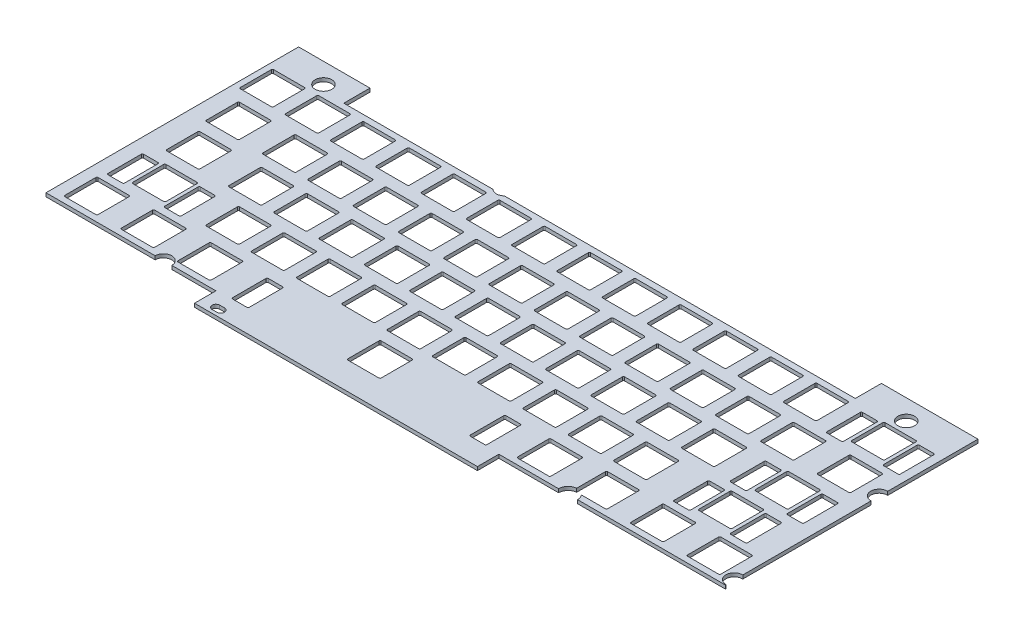
SolidWorks part; units mm, degrees
ref_plane "前视基准面" through (0, 0, 0) normal (0, 0, 1) x (1, 0, 0)
ref_plane "上视基准面" through (0, 0, 0) normal (0, 1, 0) x (1, 0, 0)
ref_plane "右视基准面" through (0, 0, 0) normal (1, 0, 0) x (0, 0, -1)
other "Configuration Table"
sketch "草图3" plane through (0, 0, 0) normal (0, 1, 0) x (1, 0, 0)
  line L0 (3.025, -2.525) -> (16.025, -2.525)
  line L1 (3.025, -16.525) -> (16.025, -16.525)
  line L2 (2.525, -3.025) -> (2.525, -16.025)
  line L3 (16.525, -3.025) -> (16.525, -16.025)
  line L4 (22.075, -2.525) -> (35.075, -2.525)
  line L5 (22.075, -16.525) -> (35.075, -16.525)
  line L6 (21.575, -3.025) -> (21.575, -16.025)
  line L7 (35.575, -3.025) -> (35.575, -16.025)
  line L8 (41.125, -2.525) -> (54.125, -2.525)
  line L9 (41.125, -16.525) -> (54.125, -16.525)
  line L10 (40.625, -3.025) -> (40.625, -16.025)
  line L11 (54.625, -3.025) -> (54.625, -16.025)
  line L12 (60.175, -2.525) -> (73.175, -2.525)
  line L13 (60.175, -16.525) -> (73.175, -16.525)
  line L14 (59.675, -3.025) -> (59.675, -16.025)
  line L15 (73.675, -3.025) -> (73.675, -16.025)
  line L16 (79.225, -2.525) -> (92.225, -2.525)
  line L17 (79.225, -16.525) -> (92.225, -16.525)
  line L18 (78.725, -3.025) -> (78.725, -16.025)
  line L19 (92.725, -3.025) -> (92.725, -16.025)
  line L20 (98.275, -2.525) -> (111.275, -2.525)
  line L21 (98.275, -16.525) -> (111.275, -16.525)
  line L22 (97.775, -3.025) -> (97.775, -16.025)
  line L23 (111.775, -3.025) -> (111.775, -16.025)
  line L24 (117.325, -2.525) -> (130.325, -2.525)
  line L25 (117.325, -16.525) -> (130.325, -16.525)
  line L26 (116.825, -3.025) -> (116.825, -16.025)
  line L27 (130.825, -3.025) -> (130.825, -16.025)
  line L28 (136.375, -2.525) -> (149.375, -2.525)
  line L29 (136.375, -16.525) -> (149.375, -16.525)
  line L30 (135.875, -3.025) -> (135.875, -16.025)
  line L31 (149.875, -3.025) -> (149.875, -16.025)
  line L32 (155.425, -2.525) -> (168.425, -2.525)
  line L33 (155.425, -16.525) -> (168.425, -16.525)
  line L34 (154.925, -3.025) -> (154.925, -16.025)
  line L35 (168.925, -3.025) -> (168.925, -16.025)
  line L36 (174.475, -2.525) -> (187.475, -2.525)
  line L37 (174.475, -16.525) -> (187.475, -16.525)
  line L38 (173.975, -3.025) -> (173.975, -16.025)
  line L39 (187.975, -3.025) -> (187.975, -16.025)
  line L40 (193.525, -2.525) -> (206.525, -2.525)
  line L41 (193.525, -16.525) -> (206.525, -16.525)
  line L42 (193.025, -3.025) -> (193.025, -16.025)
  line L43 (207.025, -3.025) -> (207.025, -16.025)
  line L44 (212.575, -2.525) -> (225.575, -2.525)
  line L45 (212.575, -16.525) -> (225.575, -16.525)
  line L46 (212.075, -3.025) -> (212.075, -16.025)
  line L47 (226.075, -3.025) -> (226.075, -16.025)
  line L48 (231.625, -2.525) -> (244.625, -2.525)
  line L49 (231.625, -16.525) -> (244.625, -16.525)
  line L50 (231.125, -3.025) -> (231.125, -16.025)
  line L51 (245.125, -3.025) -> (245.125, -16.025)
  line L52 (260.2, -2.525) -> (273.2, -2.525)
  line L53 (260.2, -16.525) -> (273.2, -16.525)
  line L54 (259.7, -3.025) -> (259.7, -16.025)
  line L55 (273.7, -3.025) -> (273.7, -16.025)
  line L56 (251.762, -3.525) -> (257.762, -3.525)
  line L57 (251.762, -18.525) -> (257.762, -18.525)
  line L58 (251.262, -4.025) -> (251.262, -18.025)
  line L59 (258.262, -4.025) -> (258.262, -18.025)
  line L60 (275.638, -3.525) -> (281.638, -3.525)
  line L61 (275.638, -18.525) -> (281.638, -18.525)
  line L62 (275.138, -4.025) -> (275.138, -18.025)
  line L63 (282.138, -4.025) -> (282.138, -18.025)
  line L64 (7.7875, -21.575) -> (20.7875, -21.575)
  line L65 (7.7875, -35.575) -> (20.7875, -35.575)
  line L66 (7.2875, -22.075) -> (7.2875, -35.075)
  line L67 (21.2875, -22.075) -> (21.2875, -35.075)
  line L68 (31.6, -21.575) -> (44.6, -21.575)
  line L69 (31.6, -35.575) -> (44.6, -35.575)
  line L70 (31.1, -22.075) -> (31.1, -35.075)
  line L71 (45.1, -22.075) -> (45.1, -35.075)
  line L72 (50.65, -21.575) -> (63.65, -21.575)
  line L73 (50.65, -35.575) -> (63.65, -35.575)
  line L74 (50.15, -22.075) -> (50.15, -35.075)
  line L75 (64.15, -22.075) -> (64.15, -35.075)
  line L76 (69.7, -21.575) -> (82.7, -21.575)
  line L77 (69.7, -35.575) -> (82.7, -35.575)
  line L78 (69.2, -22.075) -> (69.2, -35.075)
  line L79 (83.2, -22.075) -> (83.2, -35.075)
  line L80 (88.75, -21.575) -> (101.75, -21.575)
  line L81 (88.75, -35.575) -> (101.75, -35.575)
  line L82 (88.25, -22.075) -> (88.25, -35.075)
  line L83 (102.25, -22.075) -> (102.25, -35.075)
  line L84 (107.8, -21.575) -> (120.8, -21.575)
  line L85 (107.8, -35.575) -> (120.8, -35.575)
  line L86 (107.3, -22.075) -> (107.3, -35.075)
  line L87 (121.3, -22.075) -> (121.3, -35.075)
  line L88 (126.85, -21.575) -> (139.85, -21.575)
  line L89 (126.85, -35.575) -> (139.85, -35.575)
  line L90 (126.35, -22.075) -> (126.35, -35.075)
  line L91 (140.35, -22.075) -> (140.35, -35.075)
  line L92 (145.9, -21.575) -> (158.9, -21.575)
  line L93 (145.9, -35.575) -> (158.9, -35.575)
  line L94 (145.4, -22.075) -> (145.4, -35.075)
  line L95 (159.4, -22.075) -> (159.4, -35.075)
  line L96 (164.95, -21.575) -> (177.95, -21.575)
  line L97 (164.95, -35.575) -> (177.95, -35.575)
  line L98 (164.45, -22.075) -> (164.45, -35.075)
  line L99 (178.45, -22.075) -> (178.45, -35.075)
  line L100 (184, -21.575) -> (197, -21.575)
  line L101 (184, -35.575) -> (197, -35.575)
  line L102 (183.5, -22.075) -> (183.5, -35.075)
  line L103 (197.5, -22.075) -> (197.5, -35.075)
  line L104 (203.05, -21.575) -> (216.05, -21.575)
  line L105 (203.05, -35.575) -> (216.05, -35.575)
  line L106 (202.55, -22.075) -> (202.55, -35.075)
  line L107 (216.55, -22.075) -> (216.55, -35.075)
  line L108 (222.1, -21.575) -> (235.1, -21.575)
  line L109 (222.1, -35.575) -> (235.1, -35.575)
  line L110 (221.6, -22.075) -> (221.6, -35.075)
  line L111 (235.6, -22.075) -> (235.6, -35.075)
  line L112 (241.15, -21.575) -> (254.15, -21.575)
  line L113 (241.15, -35.575) -> (254.15, -35.575)
  line L114 (240.65, -22.075) -> (240.65, -35.075)
  line L115 (254.65, -22.075) -> (254.65, -35.075)
  line L116 (264.9625, -21.575) -> (277.9625, -21.575)
  line L117 (264.9625, -35.575) -> (277.9625, -35.575)
  line L118 (264.4625, -22.075) -> (264.4625, -35.075)
  line L119 (278.4625, -22.075) -> (278.4625, -35.075)
  line L120 (10.1687, -40.625) -> (23.1687, -40.625)
  line L121 (10.1687, -54.625) -> (23.1687, -54.625)
  line L122 (9.6688, -41.125) -> (9.6688, -54.125)
  line L123 (23.6687, -41.125) -> (23.6687, -54.125)
  line L124 (36.3625, -40.625) -> (49.3625, -40.625)
  line L125 (36.3625, -54.625) -> (49.3625, -54.625)
  line L126 (35.8625, -41.125) -> (35.8625, -54.125)
  line L127 (49.8625, -41.125) -> (49.8625, -54.125)
  line L128 (55.4125, -40.625) -> (68.4125, -40.625)
  line L129 (55.4125, -54.625) -> (68.4125, -54.625)
  line L130 (54.9125, -41.125) -> (54.9125, -54.125)
  line L131 (68.9125, -41.125) -> (68.9125, -54.125)
  line L132 (74.4625, -40.625) -> (87.4625, -40.625)
  line L133 (74.4625, -54.625) -> (87.4625, -54.625)
  line L134 (73.9625, -41.125) -> (73.9625, -54.125)
  line L135 (87.9625, -41.125) -> (87.9625, -54.125)
  line L136 (93.5125, -40.625) -> (106.5125, -40.625)
  line L137 (93.5125, -54.625) -> (106.5125, -54.625)
  line L138 (93.0125, -41.125) -> (93.0125, -54.125)
  line L139 (107.0125, -41.125) -> (107.0125, -54.125)
  line L140 (112.5625, -40.625) -> (125.5625, -40.625)
  line L141 (112.5625, -54.625) -> (125.5625, -54.625)
  line L142 (112.0625, -41.125) -> (112.0625, -54.125)
  line L143 (126.0625, -41.125) -> (126.0625, -54.125)
  line L144 (131.6125, -40.625) -> (144.6125, -40.625)
  line L145 (131.6125, -54.625) -> (144.6125, -54.625)
  line L146 (131.1125, -41.125) -> (131.1125, -54.125)
  line L147 (145.1125, -41.125) -> (145.1125, -54.125)
  line L148 (150.6625, -40.625) -> (163.6625, -40.625)
  line L149 (150.6625, -54.625) -> (163.6625, -54.625)
  line L150 (150.1625, -41.125) -> (150.1625, -54.125)
  line L151 (164.1625, -41.125) -> (164.1625, -54.125)
  line L152 (169.7125, -40.625) -> (182.7125, -40.625)
  line L153 (169.7125, -54.625) -> (182.7125, -54.625)
  line L154 (169.2125, -41.125) -> (169.2125, -54.125)
  line L155 (183.2125, -41.125) -> (183.2125, -54.125)
  line L156 (188.7625, -40.625) -> (201.7625, -40.625)
  line L157 (188.7625, -54.625) -> (201.7625, -54.625)
  line L158 (188.2625, -41.125) -> (188.2625, -54.125)
  line L159 (202.2625, -41.125) -> (202.2625, -54.125)
  line L160 (207.8125, -40.625) -> (220.8125, -40.625)
  line L161 (207.8125, -54.625) -> (220.8125, -54.625)
  line L162 (207.3125, -41.125) -> (207.3125, -54.125)
  line L163 (221.3125, -41.125) -> (221.3125, -54.125)
  line L164 (226.8625, -40.625) -> (239.8625, -40.625)
  line L165 (226.8625, -54.625) -> (239.8625, -54.625)
  line L166 (226.3625, -41.125) -> (226.3625, -54.125)
  line L167 (240.3625, -41.125) -> (240.3625, -54.125)
  line L168 (257.8188, -40.625) -> (270.8188, -40.625)
  line L169 (257.8188, -54.625) -> (270.8188, -54.625)
  line L170 (257.3188, -41.125) -> (257.3188, -54.125)
  line L171 (271.3188, -41.125) -> (271.3188, -54.125)
  line L172 (249.3808, -41.625) -> (255.3807, -41.625)
  line L173 (249.3808, -56.625) -> (255.3807, -56.625)
  line L174 (248.8808, -42.125) -> (248.8808, -56.125)
  line L175 (255.8807, -42.125) -> (255.8807, -56.125)
  line L176 (273.2568, -41.625) -> (279.2568, -41.625)
  line L177 (273.2568, -56.625) -> (279.2568, -56.625)
  line L178 (272.7568, -42.125) -> (272.7568, -56.125)
  line L179 (279.7568, -42.125) -> (279.7568, -56.125)
  line L180 (14.9313, -59.675) -> (27.9312, -59.675)
  line L181 (14.9313, -73.675) -> (27.9312, -73.675)
  line L182 (14.4313, -60.175) -> (14.4313, -73.175)
  line L183 (28.4312, -60.175) -> (28.4312, -73.175)
  line L184 (6.4932, -60.675) -> (12.4932, -60.675)
  line L185 (6.4932, -75.675) -> (12.4932, -75.675)
  line L186 (5.9932, -61.175) -> (5.9932, -75.175)
  line L187 (12.9932, -61.175) -> (12.9932, -75.175)
  line L188 (30.3693, -60.675) -> (36.3693, -60.675)
  line L189 (30.3693, -75.675) -> (36.3693, -75.675)
  line L190 (29.8693, -61.175) -> (29.8693, -75.175)
  line L191 (36.8693, -61.175) -> (36.8693, -75.175)
  line L192 (45.8875, -59.675) -> (58.8875, -59.675)
  line L193 (45.8875, -73.675) -> (58.8875, -73.675)
  line L194 (45.3875, -60.175) -> (45.3875, -73.175)
  line L195 (59.3875, -60.175) -> (59.3875, -73.175)
  line L196 (64.9375, -59.675) -> (77.9375, -59.675)
  line L197 (64.9375, -73.675) -> (77.9375, -73.675)
  line L198 (64.4375, -60.175) -> (64.4375, -73.175)
  line L199 (78.4375, -60.175) -> (78.4375, -73.175)
  line L200 (83.9875, -59.675) -> (96.9875, -59.675)
  line L201 (83.9875, -73.675) -> (96.9875, -73.675)
  line L202 (83.4875, -60.175) -> (83.4875, -73.175)
  line L203 (97.4875, -60.175) -> (97.4875, -73.175)
  line L204 (103.0375, -59.675) -> (116.0375, -59.675)
  line L205 (103.0375, -73.675) -> (116.0375, -73.675)
  line L206 (102.5375, -60.175) -> (102.5375, -73.175)
  line L207 (116.5375, -60.175) -> (116.5375, -73.175)
  line L208 (122.0875, -59.675) -> (135.0875, -59.675)
  line L209 (122.0875, -73.675) -> (135.0875, -73.675)
  line L210 (121.5875, -60.175) -> (121.5875, -73.175)
  line L211 (135.5875, -60.175) -> (135.5875, -73.175)
  line L212 (141.1375, -59.675) -> (154.1375, -59.675)
  line L213 (141.1375, -73.675) -> (154.1375, -73.675)
  line L214 (140.6375, -60.175) -> (140.6375, -73.175)
  line L215 (154.6375, -60.175) -> (154.6375, -73.175)
  line L216 (160.1875, -59.675) -> (173.1875, -59.675)
  line L217 (160.1875, -73.675) -> (173.1875, -73.675)
  line L218 (159.6875, -60.175) -> (159.6875, -73.175)
  line L219 (173.6875, -60.175) -> (173.6875, -73.175)
  line L220 (179.2375, -59.675) -> (192.2375, -59.675)
  line L221 (179.2375, -73.675) -> (192.2375, -73.675)
  line L222 (178.7375, -60.175) -> (178.7375, -73.175)
  line L223 (192.7375, -60.175) -> (192.7375, -73.175)
  line L224 (198.2875, -59.675) -> (211.2875, -59.675)
  line L225 (198.2875, -73.675) -> (211.2875, -73.675)
  line L226 (197.7875, -60.175) -> (197.7875, -73.175)
  line L227 (211.7875, -60.175) -> (211.7875, -73.175)
  line L228 (217.3375, -59.675) -> (230.3375, -59.675)
  line L229 (217.3375, -73.675) -> (230.3375, -73.675)
  line L230 (216.8375, -60.175) -> (216.8375, -73.175)
  line L231 (230.8375, -60.175) -> (230.8375, -73.175)
  line L232 (253.0563, -59.675) -> (266.0562, -59.675)
  line L233 (253.0563, -73.675) -> (266.0562, -73.675)
  line L234 (252.5563, -60.175) -> (252.5563, -73.175)
  line L235 (266.5562, -60.175) -> (266.5562, -73.175)
  line L236 (244.6182, -60.675) -> (250.6182, -60.675)
  line L237 (244.6182, -75.675) -> (250.6182, -75.675)
  line L238 (244.1182, -61.175) -> (244.1182, -75.175)
  line L239 (251.1182, -61.175) -> (251.1182, -75.175)
  line L240 (268.4943, -60.675) -> (274.4943, -60.675)
  line L241 (268.4943, -75.675) -> (274.4943, -75.675)
  line L242 (267.9943, -61.175) -> (267.9943, -75.175)
  line L243 (274.9943, -61.175) -> (274.9943, -75.175)
  line L244 (5.4063, -78.725) -> (18.4062, -78.725)
  line L245 (5.4063, -92.725) -> (18.4062, -92.725)
  line L246 (4.9062, -79.225) -> (4.9062, -92.225)
  line L247 (18.9062, -79.225) -> (18.9062, -92.225)
  line L248 (29.2188, -78.725) -> (42.2188, -78.725)
  line L249 (29.2188, -92.725) -> (42.2188, -92.725)
  line L250 (28.7188, -79.225) -> (28.7188, -92.225)
  line L251 (42.7188, -79.225) -> (42.7188, -92.225)
  line L252 (53.0312, -78.725) -> (66.0312, -78.725)
  line L253 (53.0312, -92.725) -> (66.0312, -92.725)
  line L254 (52.5312, -79.225) -> (52.5312, -92.225)
  line L255 (66.5312, -79.225) -> (66.5312, -92.225)
  line L256 (124.4688, -78.725) -> (137.4688, -78.725)
  line L257 (124.4688, -92.725) -> (137.4688, -92.725)
  line L258 (123.9688, -79.225) -> (123.9688, -92.225)
  line L259 (137.9688, -79.225) -> (137.9688, -92.225)
  line L260 (77.9688, -79.725) -> (83.9688, -79.725)
  line L261 (77.9688, -94.725) -> (83.9688, -94.725)
  line L262 (77.4688, -80.225) -> (77.4688, -94.225)
  line L263 (84.4688, -80.225) -> (84.4688, -94.225)
  line L264 (177.9688, -79.725) -> (183.9688, -79.725)
  line L265 (177.9688, -94.725) -> (183.9688, -94.725)
  line L266 (177.4688, -80.225) -> (177.4688, -94.225)
  line L267 (184.4688, -80.225) -> (184.4688, -94.225)
  line L268 (195.9062, -78.725) -> (208.9063, -78.725)
  line L269 (195.9062, -92.725) -> (208.9063, -92.725)
  line L270 (195.4062, -79.225) -> (195.4062, -92.225)
  line L271 (209.4063, -79.225) -> (209.4063, -92.225)
  line L272 (219.7188, -78.725) -> (232.7188, -78.725)
  line L273 (219.7188, -92.725) -> (232.7188, -92.725)
  line L274 (219.2188, -79.225) -> (219.2188, -92.225)
  line L275 (233.2188, -79.225) -> (233.2188, -92.225)
  line L276 (243.5312, -78.725) -> (256.5312, -78.725)
  line L277 (243.5312, -92.725) -> (256.5312, -92.725)
  line L278 (243.0312, -79.225) -> (243.0312, -92.225)
  line L279 (257.0312, -79.225) -> (257.0312, -92.225)
  line L280 (267.3438, -78.725) -> (280.3438, -78.725)
  line L281 (267.3438, -92.725) -> (280.3438, -92.725)
  line L282 (266.8438, -79.225) -> (266.8438, -92.225)
  line L283 (280.8438, -79.225) -> (280.8438, -92.225)
  line L284 (0, -95.25) -> (285.75, -95.25)
  line L285 (0, 0) -> (285.75, 0)
  line L286 (0, -95.25) -> (0, 0)
  line L287 (285.75, -95.25) -> (285.75, 0)
  arc A0 (3.025, -2.525) -> (2.525, -3.025) centre (3.025, -3.025) ccw
  arc A1 (16.525, -3.025) -> (16.025, -2.525) centre (16.025, -3.025) ccw
  arc A2 (2.525, -16.025) -> (3.025, -16.525) centre (3.025, -16.025) ccw
  arc A3 (16.025, -16.525) -> (16.525, -16.025) centre (16.025, -16.025) ccw
  arc A4 (22.075, -2.525) -> (21.575, -3.025) centre (22.075, -3.025) ccw
  arc A5 (35.575, -3.025) -> (35.075, -2.525) centre (35.075, -3.025) ccw
  arc A6 (21.575, -16.025) -> (22.075, -16.525) centre (22.075, -16.025) ccw
  arc A7 (35.075, -16.525) -> (35.575, -16.025) centre (35.075, -16.025) ccw
  arc A8 (41.125, -2.525) -> (40.625, -3.025) centre (41.125, -3.025) ccw
  arc A9 (54.625, -3.025) -> (54.125, -2.525) centre (54.125, -3.025) ccw
  arc A10 (40.625, -16.025) -> (41.125, -16.525) centre (41.125, -16.025) ccw
  arc A11 (54.125, -16.525) -> (54.625, -16.025) centre (54.125, -16.025) ccw
  arc A12 (60.175, -2.525) -> (59.675, -3.025) centre (60.175, -3.025) ccw
  arc A13 (73.675, -3.025) -> (73.175, -2.525) centre (73.175, -3.025) ccw
  arc A14 (59.675, -16.025) -> (60.175, -16.525) centre (60.175, -16.025) ccw
  arc A15 (73.175, -16.525) -> (73.675, -16.025) centre (73.175, -16.025) ccw
  arc A16 (79.225, -2.525) -> (78.725, -3.025) centre (79.225, -3.025) ccw
  arc A17 (92.725, -3.025) -> (92.225, -2.525) centre (92.225, -3.025) ccw
  arc A18 (78.725, -16.025) -> (79.225, -16.525) centre (79.225, -16.025) ccw
  arc A19 (92.225, -16.525) -> (92.725, -16.025) centre (92.225, -16.025) ccw
  arc A20 (98.275, -2.525) -> (97.775, -3.025) centre (98.275, -3.025) ccw
  arc A21 (111.775, -3.025) -> (111.275, -2.525) centre (111.275, -3.025) ccw
  arc A22 (97.775, -16.025) -> (98.275, -16.525) centre (98.275, -16.025) ccw
  arc A23 (111.275, -16.525) -> (111.775, -16.025) centre (111.275, -16.025) ccw
  arc A24 (117.325, -2.525) -> (116.825, -3.025) centre (117.325, -3.025) ccw
  arc A25 (130.825, -3.025) -> (130.325, -2.525) centre (130.325, -3.025) ccw
  arc A26 (116.825, -16.025) -> (117.325, -16.525) centre (117.325, -16.025) ccw
  arc A27 (130.325, -16.525) -> (130.825, -16.025) centre (130.325, -16.025) ccw
  arc A28 (136.375, -2.525) -> (135.875, -3.025) centre (136.375, -3.025) ccw
  arc A29 (149.875, -3.025) -> (149.375, -2.525) centre (149.375, -3.025) ccw
  arc A30 (135.875, -16.025) -> (136.375, -16.525) centre (136.375, -16.025) ccw
  arc A31 (149.375, -16.525) -> (149.875, -16.025) centre (149.375, -16.025) ccw
  arc A32 (155.425, -2.525) -> (154.925, -3.025) centre (155.425, -3.025) ccw
  arc A33 (168.925, -3.025) -> (168.425, -2.525) centre (168.425, -3.025) ccw
  arc A34 (154.925, -16.025) -> (155.425, -16.525) centre (155.425, -16.025) ccw
  arc A35 (168.425, -16.525) -> (168.925, -16.025) centre (168.425, -16.025) ccw
  arc A36 (174.475, -2.525) -> (173.975, -3.025) centre (174.475, -3.025) ccw
  arc A37 (187.975, -3.025) -> (187.475, -2.525) centre (187.475, -3.025) ccw
  arc A38 (173.975, -16.025) -> (174.475, -16.525) centre (174.475, -16.025) ccw
  arc A39 (187.475, -16.525) -> (187.975, -16.025) centre (187.475, -16.025) ccw
  arc A40 (193.525, -2.525) -> (193.025, -3.025) centre (193.525, -3.025) ccw
  arc A41 (207.025, -3.025) -> (206.525, -2.525) centre (206.525, -3.025) ccw
  arc A42 (193.025, -16.025) -> (193.525, -16.525) centre (193.525, -16.025) ccw
  arc A43 (206.525, -16.525) -> (207.025, -16.025) centre (206.525, -16.025) ccw
  arc A44 (212.575, -2.525) -> (212.075, -3.025) centre (212.575, -3.025) ccw
  arc A45 (226.075, -3.025) -> (225.575, -2.525) centre (225.575, -3.025) ccw
  arc A46 (212.075, -16.025) -> (212.575, -16.525) centre (212.575, -16.025) ccw
  arc A47 (225.575, -16.525) -> (226.075, -16.025) centre (225.575, -16.025) ccw
  arc A48 (231.625, -2.525) -> (231.125, -3.025) centre (231.625, -3.025) ccw
  arc A49 (245.125, -3.025) -> (244.625, -2.525) centre (244.625, -3.025) ccw
  arc A50 (231.125, -16.025) -> (231.625, -16.525) centre (231.625, -16.025) ccw
  arc A51 (244.625, -16.525) -> (245.125, -16.025) centre (244.625, -16.025) ccw
  arc A52 (260.2, -2.525) -> (259.7, -3.025) centre (260.2, -3.025) ccw
  arc A53 (273.7, -3.025) -> (273.2, -2.525) centre (273.2, -3.025) ccw
  arc A54 (259.7, -16.025) -> (260.2, -16.525) centre (260.2, -16.025) ccw
  arc A55 (273.2, -16.525) -> (273.7, -16.025) centre (273.2, -16.025) ccw
  arc A56 (251.762, -3.525) -> (251.262, -4.025) centre (251.762, -4.025) ccw
  arc A57 (258.262, -4.025) -> (257.762, -3.525) centre (257.762, -4.025) ccw
  arc A58 (251.262, -18.025) -> (251.762, -18.525) centre (251.762, -18.025) ccw
  arc A59 (257.762, -18.525) -> (258.262, -18.025) centre (257.762, -18.025) ccw
  arc A60 (275.638, -3.525) -> (275.138, -4.025) centre (275.638, -4.025) ccw
  arc A61 (282.138, -4.025) -> (281.638, -3.525) centre (281.638, -4.025) ccw
  arc A62 (275.138, -18.025) -> (275.638, -18.525) centre (275.638, -18.025) ccw
  arc A63 (281.638, -18.525) -> (282.138, -18.025) centre (281.638, -18.025) ccw
  arc A64 (7.7875, -21.575) -> (7.2875, -22.075) centre (7.7875, -22.075) ccw
  arc A65 (21.2875, -22.075) -> (20.7875, -21.575) centre (20.7875, -22.075) ccw
  arc A66 (7.2875, -35.075) -> (7.7875, -35.575) centre (7.7875, -35.075) ccw
  arc A67 (20.7875, -35.575) -> (21.2875, -35.075) centre (20.7875, -35.075) ccw
  arc A68 (31.6, -21.575) -> (31.1, -22.075) centre (31.6, -22.075) ccw
  arc A69 (45.1, -22.075) -> (44.6, -21.575) centre (44.6, -22.075) ccw
  arc A70 (31.1, -35.075) -> (31.6, -35.575) centre (31.6, -35.075) ccw
  arc A71 (44.6, -35.575) -> (45.1, -35.075) centre (44.6, -35.075) ccw
  arc A72 (50.65, -21.575) -> (50.15, -22.075) centre (50.65, -22.075) ccw
  arc A73 (64.15, -22.075) -> (63.65, -21.575) centre (63.65, -22.075) ccw
  arc A74 (50.15, -35.075) -> (50.65, -35.575) centre (50.65, -35.075) ccw
  arc A75 (63.65, -35.575) -> (64.15, -35.075) centre (63.65, -35.075) ccw
  arc A76 (69.7, -21.575) -> (69.2, -22.075) centre (69.7, -22.075) ccw
  arc A77 (83.2, -22.075) -> (82.7, -21.575) centre (82.7, -22.075) ccw
  arc A78 (69.2, -35.075) -> (69.7, -35.575) centre (69.7, -35.075) ccw
  arc A79 (82.7, -35.575) -> (83.2, -35.075) centre (82.7, -35.075) ccw
  arc A80 (88.75, -21.575) -> (88.25, -22.075) centre (88.75, -22.075) ccw
  arc A81 (102.25, -22.075) -> (101.75, -21.575) centre (101.75, -22.075) ccw
  arc A82 (88.25, -35.075) -> (88.75, -35.575) centre (88.75, -35.075) ccw
  arc A83 (101.75, -35.575) -> (102.25, -35.075) centre (101.75, -35.075) ccw
  arc A84 (107.8, -21.575) -> (107.3, -22.075) centre (107.8, -22.075) ccw
  arc A85 (121.3, -22.075) -> (120.8, -21.575) centre (120.8, -22.075) ccw
  arc A86 (107.3, -35.075) -> (107.8, -35.575) centre (107.8, -35.075) ccw
  arc A87 (120.8, -35.575) -> (121.3, -35.075) centre (120.8, -35.075) ccw
  arc A88 (126.85, -21.575) -> (126.35, -22.075) centre (126.85, -22.075) ccw
  arc A89 (140.35, -22.075) -> (139.85, -21.575) centre (139.85, -22.075) ccw
  arc A90 (126.35, -35.075) -> (126.85, -35.575) centre (126.85, -35.075) ccw
  arc A91 (139.85, -35.575) -> (140.35, -35.075) centre (139.85, -35.075) ccw
  arc A92 (145.9, -21.575) -> (145.4, -22.075) centre (145.9, -22.075) ccw
  arc A93 (159.4, -22.075) -> (158.9, -21.575) centre (158.9, -22.075) ccw
  arc A94 (145.4, -35.075) -> (145.9, -35.575) centre (145.9, -35.075) ccw
  arc A95 (158.9, -35.575) -> (159.4, -35.075) centre (158.9, -35.075) ccw
  arc A96 (164.95, -21.575) -> (164.45, -22.075) centre (164.95, -22.075) ccw
  arc A97 (178.45, -22.075) -> (177.95, -21.575) centre (177.95, -22.075) ccw
  arc A98 (164.45, -35.075) -> (164.95, -35.575) centre (164.95, -35.075) ccw
  arc A99 (177.95, -35.575) -> (178.45, -35.075) centre (177.95, -35.075) ccw
  arc A100 (184, -21.575) -> (183.5, -22.075) centre (184, -22.075) ccw
  arc A101 (197.5, -22.075) -> (197, -21.575) centre (197, -22.075) ccw
  arc A102 (183.5, -35.075) -> (184, -35.575) centre (184, -35.075) ccw
  arc A103 (197, -35.575) -> (197.5, -35.075) centre (197, -35.075) ccw
  arc A104 (203.05, -21.575) -> (202.55, -22.075) centre (203.05, -22.075) ccw
  arc A105 (216.55, -22.075) -> (216.05, -21.575) centre (216.05, -22.075) ccw
  arc A106 (202.55, -35.075) -> (203.05, -35.575) centre (203.05, -35.075) ccw
  arc A107 (216.05, -35.575) -> (216.55, -35.075) centre (216.05, -35.075) ccw
  arc A108 (222.1, -21.575) -> (221.6, -22.075) centre (222.1, -22.075) ccw
  arc A109 (235.6, -22.075) -> (235.1, -21.575) centre (235.1, -22.075) ccw
  arc A110 (221.6, -35.075) -> (222.1, -35.575) centre (222.1, -35.075) ccw
  arc A111 (235.1, -35.575) -> (235.6, -35.075) centre (235.1, -35.075) ccw
  arc A112 (241.15, -21.575) -> (240.65, -22.075) centre (241.15, -22.075) ccw
  arc A113 (254.65, -22.075) -> (254.15, -21.575) centre (254.15, -22.075) ccw
  arc A114 (240.65, -35.075) -> (241.15, -35.575) centre (241.15, -35.075) ccw
  arc A115 (254.15, -35.575) -> (254.65, -35.075) centre (254.15, -35.075) ccw
  arc A116 (264.9625, -21.575) -> (264.4625, -22.075) centre (264.9625, -22.075) ccw
  arc A117 (278.4625, -22.075) -> (277.9625, -21.575) centre (277.9625, -22.075) ccw
  arc A118 (264.4625, -35.075) -> (264.9625, -35.575) centre (264.9625, -35.075) ccw
  arc A119 (277.9625, -35.575) -> (278.4625, -35.075) centre (277.9625, -35.075) ccw
  arc A120 (10.1687, -40.625) -> (9.6688, -41.125) centre (10.1687, -41.125) ccw
  arc A121 (23.6687, -41.125) -> (23.1687, -40.625) centre (23.1687, -41.125) ccw
  arc A122 (9.6688, -54.125) -> (10.1687, -54.625) centre (10.1687, -54.125) ccw
  arc A123 (23.1687, -54.625) -> (23.6687, -54.125) centre (23.1687, -54.125) ccw
  arc A124 (36.3625, -40.625) -> (35.8625, -41.125) centre (36.3625, -41.125) ccw
  arc A125 (49.8625, -41.125) -> (49.3625, -40.625) centre (49.3625, -41.125) ccw
  arc A126 (35.8625, -54.125) -> (36.3625, -54.625) centre (36.3625, -54.125) ccw
  arc A127 (49.3625, -54.625) -> (49.8625, -54.125) centre (49.3625, -54.125) ccw
  arc A128 (55.4125, -40.625) -> (54.9125, -41.125) centre (55.4125, -41.125) ccw
  arc A129 (68.9125, -41.125) -> (68.4125, -40.625) centre (68.4125, -41.125) ccw
  arc A130 (54.9125, -54.125) -> (55.4125, -54.625) centre (55.4125, -54.125) ccw
  arc A131 (68.4125, -54.625) -> (68.9125, -54.125) centre (68.4125, -54.125) ccw
  arc A132 (74.4625, -40.625) -> (73.9625, -41.125) centre (74.4625, -41.125) ccw
  arc A133 (87.9625, -41.125) -> (87.4625, -40.625) centre (87.4625, -41.125) ccw
  arc A134 (73.9625, -54.125) -> (74.4625, -54.625) centre (74.4625, -54.125) ccw
  arc A135 (87.4625, -54.625) -> (87.9625, -54.125) centre (87.4625, -54.125) ccw
  arc A136 (93.5125, -40.625) -> (93.0125, -41.125) centre (93.5125, -41.125) ccw
  arc A137 (107.0125, -41.125) -> (106.5125, -40.625) centre (106.5125, -41.125) ccw
  arc A138 (93.0125, -54.125) -> (93.5125, -54.625) centre (93.5125, -54.125) ccw
  arc A139 (106.5125, -54.625) -> (107.0125, -54.125) centre (106.5125, -54.125) ccw
  arc A140 (112.5625, -40.625) -> (112.0625, -41.125) centre (112.5625, -41.125) ccw
  arc A141 (126.0625, -41.125) -> (125.5625, -40.625) centre (125.5625, -41.125) ccw
  arc A142 (112.0625, -54.125) -> (112.5625, -54.625) centre (112.5625, -54.125) ccw
  arc A143 (125.5625, -54.625) -> (126.0625, -54.125) centre (125.5625, -54.125) ccw
  arc A144 (131.6125, -40.625) -> (131.1125, -41.125) centre (131.6125, -41.125) ccw
  arc A145 (145.1125, -41.125) -> (144.6125, -40.625) centre (144.6125, -41.125) ccw
  arc A146 (131.1125, -54.125) -> (131.6125, -54.625) centre (131.6125, -54.125) ccw
  arc A147 (144.6125, -54.625) -> (145.1125, -54.125) centre (144.6125, -54.125) ccw
  arc A148 (150.6625, -40.625) -> (150.1625, -41.125) centre (150.6625, -41.125) ccw
  arc A149 (164.1625, -41.125) -> (163.6625, -40.625) centre (163.6625, -41.125) ccw
  arc A150 (150.1625, -54.125) -> (150.6625, -54.625) centre (150.6625, -54.125) ccw
  arc A151 (163.6625, -54.625) -> (164.1625, -54.125) centre (163.6625, -54.125) ccw
  arc A152 (169.7125, -40.625) -> (169.2125, -41.125) centre (169.7125, -41.125) ccw
  arc A153 (183.2125, -41.125) -> (182.7125, -40.625) centre (182.7125, -41.125) ccw
  arc A154 (169.2125, -54.125) -> (169.7125, -54.625) centre (169.7125, -54.125) ccw
  arc A155 (182.7125, -54.625) -> (183.2125, -54.125) centre (182.7125, -54.125) ccw
  arc A156 (188.7625, -40.625) -> (188.2625, -41.125) centre (188.7625, -41.125) ccw
  arc A157 (202.2625, -41.125) -> (201.7625, -40.625) centre (201.7625, -41.125) ccw
  arc A158 (188.2625, -54.125) -> (188.7625, -54.625) centre (188.7625, -54.125) ccw
  arc A159 (201.7625, -54.625) -> (202.2625, -54.125) centre (201.7625, -54.125) ccw
  arc A160 (207.8125, -40.625) -> (207.3125, -41.125) centre (207.8125, -41.125) ccw
  arc A161 (221.3125, -41.125) -> (220.8125, -40.625) centre (220.8125, -41.125) ccw
  arc A162 (207.3125, -54.125) -> (207.8125, -54.625) centre (207.8125, -54.125) ccw
  arc A163 (220.8125, -54.625) -> (221.3125, -54.125) centre (220.8125, -54.125) ccw
  arc A164 (226.8625, -40.625) -> (226.3625, -41.125) centre (226.8625, -41.125) ccw
  arc A165 (240.3625, -41.125) -> (239.8625, -40.625) centre (239.8625, -41.125) ccw
  arc A166 (226.3625, -54.125) -> (226.8625, -54.625) centre (226.8625, -54.125) ccw
  arc A167 (239.8625, -54.625) -> (240.3625, -54.125) centre (239.8625, -54.125) ccw
  arc A168 (257.8188, -40.625) -> (257.3188, -41.125) centre (257.8188, -41.125) ccw
  arc A169 (271.3188, -41.125) -> (270.8188, -40.625) centre (270.8188, -41.125) ccw
  arc A170 (257.3188, -54.125) -> (257.8188, -54.625) centre (257.8188, -54.125) ccw
  arc A171 (270.8188, -54.625) -> (271.3188, -54.125) centre (270.8188, -54.125) ccw
  arc A172 (249.3808, -41.625) -> (248.8808, -42.125) centre (249.3808, -42.125) ccw
  arc A173 (255.8807, -42.125) -> (255.3807, -41.625) centre (255.3807, -42.125) ccw
  arc A174 (248.8808, -56.125) -> (249.3808, -56.625) centre (249.3808, -56.125) ccw
  arc A175 (255.3807, -56.625) -> (255.8807, -56.125) centre (255.3807, -56.125) ccw
  arc A176 (273.2568, -41.625) -> (272.7568, -42.125) centre (273.2568, -42.125) ccw
  arc A177 (279.7568, -42.125) -> (279.2568, -41.625) centre (279.2568, -42.125) ccw
  arc A178 (272.7568, -56.125) -> (273.2568, -56.625) centre (273.2568, -56.125) ccw
  arc A179 (279.2568, -56.625) -> (279.7568, -56.125) centre (279.2568, -56.125) ccw
  arc A180 (14.9313, -59.675) -> (14.4313, -60.175) centre (14.9313, -60.175) ccw
  arc A181 (28.4312, -60.175) -> (27.9312, -59.675) centre (27.9312, -60.175) ccw
  arc A182 (14.4313, -73.175) -> (14.9313, -73.675) centre (14.9313, -73.175) ccw
  arc A183 (27.9312, -73.675) -> (28.4312, -73.175) centre (27.9312, -73.175) ccw
  arc A184 (6.4932, -60.675) -> (5.9932, -61.175) centre (6.4932, -61.175) ccw
  arc A185 (12.9932, -61.175) -> (12.4932, -60.675) centre (12.4932, -61.175) ccw
  arc A186 (5.9932, -75.175) -> (6.4932, -75.675) centre (6.4932, -75.175) ccw
  arc A187 (12.4932, -75.675) -> (12.9932, -75.175) centre (12.4932, -75.175) ccw
  arc A188 (30.3693, -60.675) -> (29.8693, -61.175) centre (30.3693, -61.175) ccw
  arc A189 (36.8693, -61.175) -> (36.3693, -60.675) centre (36.3693, -61.175) ccw
  arc A190 (29.8693, -75.175) -> (30.3693, -75.675) centre (30.3693, -75.175) ccw
  arc A191 (36.3693, -75.675) -> (36.8693, -75.175) centre (36.3693, -75.175) ccw
  arc A192 (45.8875, -59.675) -> (45.3875, -60.175) centre (45.8875, -60.175) ccw
  arc A193 (59.3875, -60.175) -> (58.8875, -59.675) centre (58.8875, -60.175) ccw
  arc A194 (45.3875, -73.175) -> (45.8875, -73.675) centre (45.8875, -73.175) ccw
  arc A195 (58.8875, -73.675) -> (59.3875, -73.175) centre (58.8875, -73.175) ccw
  arc A196 (64.9375, -59.675) -> (64.4375, -60.175) centre (64.9375, -60.175) ccw
  arc A197 (78.4375, -60.175) -> (77.9375, -59.675) centre (77.9375, -60.175) ccw
  arc A198 (64.4375, -73.175) -> (64.9375, -73.675) centre (64.9375, -73.175) ccw
  arc A199 (77.9375, -73.675) -> (78.4375, -73.175) centre (77.9375, -73.175) ccw
  arc A200 (83.9875, -59.675) -> (83.4875, -60.175) centre (83.9875, -60.175) ccw
  arc A201 (97.4875, -60.175) -> (96.9875, -59.675) centre (96.9875, -60.175) ccw
  arc A202 (83.4875, -73.175) -> (83.9875, -73.675) centre (83.9875, -73.175) ccw
  arc A203 (96.9875, -73.675) -> (97.4875, -73.175) centre (96.9875, -73.175) ccw
  arc A204 (103.0375, -59.675) -> (102.5375, -60.175) centre (103.0375, -60.175) ccw
  arc A205 (116.5375, -60.175) -> (116.0375, -59.675) centre (116.0375, -60.175) ccw
  arc A206 (102.5375, -73.175) -> (103.0375, -73.675) centre (103.0375, -73.175) ccw
  arc A207 (116.0375, -73.675) -> (116.5375, -73.175) centre (116.0375, -73.175) ccw
  arc A208 (122.0875, -59.675) -> (121.5875, -60.175) centre (122.0875, -60.175) ccw
  arc A209 (135.5875, -60.175) -> (135.0875, -59.675) centre (135.0875, -60.175) ccw
  arc A210 (121.5875, -73.175) -> (122.0875, -73.675) centre (122.0875, -73.175) ccw
  arc A211 (135.0875, -73.675) -> (135.5875, -73.175) centre (135.0875, -73.175) ccw
  arc A212 (141.1375, -59.675) -> (140.6375, -60.175) centre (141.1375, -60.175) ccw
  arc A213 (154.6375, -60.175) -> (154.1375, -59.675) centre (154.1375, -60.175) ccw
  arc A214 (140.6375, -73.175) -> (141.1375, -73.675) centre (141.1375, -73.175) ccw
  arc A215 (154.1375, -73.675) -> (154.6375, -73.175) centre (154.1375, -73.175) ccw
  arc A216 (160.1875, -59.675) -> (159.6875, -60.175) centre (160.1875, -60.175) ccw
  arc A217 (173.6875, -60.175) -> (173.1875, -59.675) centre (173.1875, -60.175) ccw
  arc A218 (159.6875, -73.175) -> (160.1875, -73.675) centre (160.1875, -73.175) ccw
  arc A219 (173.1875, -73.675) -> (173.6875, -73.175) centre (173.1875, -73.175) ccw
  arc A220 (179.2375, -59.675) -> (178.7375, -60.175) centre (179.2375, -60.175) ccw
  arc A221 (192.7375, -60.175) -> (192.2375, -59.675) centre (192.2375, -60.175) ccw
  arc A222 (178.7375, -73.175) -> (179.2375, -73.675) centre (179.2375, -73.175) ccw
  arc A223 (192.2375, -73.675) -> (192.7375, -73.175) centre (192.2375, -73.175) ccw
  arc A224 (198.2875, -59.675) -> (197.7875, -60.175) centre (198.2875, -60.175) ccw
  arc A225 (211.7875, -60.175) -> (211.2875, -59.675) centre (211.2875, -60.175) ccw
  arc A226 (197.7875, -73.175) -> (198.2875, -73.675) centre (198.2875, -73.175) ccw
  arc A227 (211.2875, -73.675) -> (211.7875, -73.175) centre (211.2875, -73.175) ccw
  arc A228 (217.3375, -59.675) -> (216.8375, -60.175) centre (217.3375, -60.175) ccw
  arc A229 (230.8375, -60.175) -> (230.3375, -59.675) centre (230.3375, -60.175) ccw
  arc A230 (216.8375, -73.175) -> (217.3375, -73.675) centre (217.3375, -73.175) ccw
  arc A231 (230.3375, -73.675) -> (230.8375, -73.175) centre (230.3375, -73.175) ccw
  arc A232 (253.0563, -59.675) -> (252.5563, -60.175) centre (253.0563, -60.175) ccw
  arc A233 (266.5562, -60.175) -> (266.0562, -59.675) centre (266.0562, -60.175) ccw
  arc A234 (252.5563, -73.175) -> (253.0563, -73.675) centre (253.0563, -73.175) ccw
  arc A235 (266.0562, -73.675) -> (266.5562, -73.175) centre (266.0562, -73.175) ccw
  arc A236 (244.6182, -60.675) -> (244.1182, -61.175) centre (244.6182, -61.175) ccw
  arc A237 (251.1182, -61.175) -> (250.6182, -60.675) centre (250.6182, -61.175) ccw
  arc A238 (244.1182, -75.175) -> (244.6182, -75.675) centre (244.6182, -75.175) ccw
  arc A239 (250.6182, -75.675) -> (251.1182, -75.175) centre (250.6182, -75.175) ccw
  arc A240 (268.4943, -60.675) -> (267.9943, -61.175) centre (268.4943, -61.175) ccw
  arc A241 (274.9943, -61.175) -> (274.4943, -60.675) centre (274.4943, -61.175) ccw
  arc A242 (267.9943, -75.175) -> (268.4943, -75.675) centre (268.4943, -75.175) ccw
  arc A243 (274.4943, -75.675) -> (274.9943, -75.175) centre (274.4943, -75.175) ccw
  arc A244 (5.4063, -78.725) -> (4.9062, -79.225) centre (5.4063, -79.225) ccw
  arc A245 (18.9062, -79.225) -> (18.4062, -78.725) centre (18.4062, -79.225) ccw
  arc A246 (4.9062, -92.225) -> (5.4063, -92.725) centre (5.4063, -92.225) ccw
  arc A247 (18.4062, -92.725) -> (18.9062, -92.225) centre (18.4062, -92.225) ccw
  arc A248 (29.2188, -78.725) -> (28.7188, -79.225) centre (29.2188, -79.225) ccw
  arc A249 (42.7188, -79.225) -> (42.2188, -78.725) centre (42.2188, -79.225) ccw
  arc A250 (28.7188, -92.225) -> (29.2188, -92.725) centre (29.2188, -92.225) ccw
  arc A251 (42.2188, -92.725) -> (42.7188, -92.225) centre (42.2188, -92.225) ccw
  arc A252 (53.0312, -78.725) -> (52.5312, -79.225) centre (53.0312, -79.225) ccw
  arc A253 (66.5312, -79.225) -> (66.0312, -78.725) centre (66.0312, -79.225) ccw
  arc A254 (52.5312, -92.225) -> (53.0312, -92.725) centre (53.0312, -92.225) ccw
  arc A255 (66.0312, -92.725) -> (66.5312, -92.225) centre (66.0312, -92.225) ccw
  arc A256 (124.4688, -78.725) -> (123.9688, -79.225) centre (124.4688, -79.225) ccw
  arc A257 (137.9688, -79.225) -> (137.4688, -78.725) centre (137.4688, -79.225) ccw
  arc A258 (123.9688, -92.225) -> (124.4688, -92.725) centre (124.4688, -92.225) ccw
  arc A259 (137.4688, -92.725) -> (137.9688, -92.225) centre (137.4688, -92.225) ccw
  arc A260 (77.9688, -79.725) -> (77.4688, -80.225) centre (77.9688, -80.225) ccw
  arc A261 (84.4688, -80.225) -> (83.9688, -79.725) centre (83.9688, -80.225) ccw
  arc A262 (77.4688, -94.225) -> (77.9688, -94.725) centre (77.9688, -94.225) ccw
  arc A263 (83.9688, -94.725) -> (84.4688, -94.225) centre (83.9688, -94.225) ccw
  arc A264 (177.9688, -79.725) -> (177.4688, -80.225) centre (177.9688, -80.225) ccw
  arc A265 (184.4688, -80.225) -> (183.9688, -79.725) centre (183.9688, -80.225) ccw
  arc A266 (177.4688, -94.225) -> (177.9688, -94.725) centre (177.9688, -94.225) ccw
  arc A267 (183.9688, -94.725) -> (184.4688, -94.225) centre (183.9688, -94.225) ccw
  arc A268 (195.9062, -78.725) -> (195.4062, -79.225) centre (195.9062, -79.225) ccw
  arc A269 (209.4063, -79.225) -> (208.9063, -78.725) centre (208.9063, -79.225) ccw
  arc A270 (195.4062, -92.225) -> (195.9062, -92.725) centre (195.9062, -92.225) ccw
  arc A271 (208.9063, -92.725) -> (209.4063, -92.225) centre (208.9063, -92.225) ccw
  arc A272 (219.7188, -78.725) -> (219.2188, -79.225) centre (219.7188, -79.225) ccw
  arc A273 (233.2188, -79.225) -> (232.7188, -78.725) centre (232.7188, -79.225) ccw
  arc A274 (219.2188, -92.225) -> (219.7188, -92.725) centre (219.7188, -92.225) ccw
  arc A275 (232.7188, -92.725) -> (233.2188, -92.225) centre (232.7188, -92.225) ccw
  arc A276 (243.5312, -78.725) -> (243.0312, -79.225) centre (243.5312, -79.225) ccw
  arc A277 (257.0312, -79.225) -> (256.5312, -78.725) centre (256.5312, -79.225) ccw
  arc A278 (243.0312, -92.225) -> (243.5312, -92.725) centre (243.5312, -92.225) ccw
  arc A279 (256.5312, -92.725) -> (257.0312, -92.225) centre (256.5312, -92.225) ccw
  arc A280 (267.3438, -78.725) -> (266.8438, -79.225) centre (267.3438, -79.225) ccw
  arc A281 (280.8438, -79.225) -> (280.3438, -78.725) centre (280.3438, -79.225) ccw
  arc A282 (266.8438, -92.225) -> (267.3438, -92.725) centre (267.3438, -92.225) ccw
  arc A283 (280.3438, -92.725) -> (280.8438, -92.225) centre (280.3438, -92.225) ccw
extrude "凸台-拉伸2" add sketch "草图3" along normal blind 1.5
sketch "草图4" plane through (0, 1.5, 0) normal (0, 1, 0) x (1, 0, 0)
  circle A0 centre (49.403, -95.25) radius 3.5
  circle A1 centre (219.583, -95.25) radius 4
  circle A2 centre (285.623, -91.44) radius 3.5
  circle A3 centre (18.923, 2.54) radius 3.5
  circle A4 centre (285.623, -30.48) radius 3.5
  circle A5 centre (264.033, 2.54) radius 3.5
  circle A6 centre (95.123, 2.54) radius 3.5
  dimension "D1" = 7
  dimension "D2" = 8
  dimension "D3" = 7
  dimension "D4" = 7
  dimension "D5" = 7
  dimension "D6" = 7
  dimension "D7" = 7
extrude "切除-拉伸1" cut sketch "草图4" against normal up to next
sketch "草图5" plane through (0, 1.5, 0) normal (0, 1, 0) x (1, 0, 0)
  line L0 (77.4688, -80.225) -> (77.4688, -94.225) construction
  line L1 (71.4688, -95.25) -> (190.4688, -95.25)
  line L2 (71.4688, -95.25) -> (71.4688, -104.25)
  line L3 (71.4688, -104.25) -> (190.4688, -104.25)
  line L4 (190.4688, -95.25) -> (190.4688, -104.25)
  line L5 (184.4688, -94.225) -> (184.4688, -80.225) construction
  line L6 (52.903, -95.25) -> (215.583, -95.25) construction
  line L7 (21.331, 0) -> (30, 0)
  line L8 (0, 0) -> (16.515, 0)
  line L9 (0, 0) -> (0, 11)
  line L10 (0, 11) -> (30, 11)
  line L11 (30, 0) -> (30, 11)
  line L12 (245.125, -16.025) -> (245.125, -3.025) construction
  line L13 (285.75, 0) -> (266.441, 0)
  line L14 (285.75, 0) -> (285.75, 11)
  line L15 (285.75, 11) -> (245.125, 11)
  line L16 (245.125, 0) -> (245.125, 11)
  line L17 (261.625, 0) -> (245.125, 0)
  arc A0 (21.331, 0) -> (16.515, 0) centre (18.923, 2.54) ccw
  arc A1 (16.515, 0) -> (21.331, 0) centre (18.923, 2.54) ccw construction
  arc A2 (266.441, 0) -> (261.625, 0) centre (264.033, 2.54) ccw
  arc A3 (261.625, 0) -> (266.441, 0) centre (264.033, 2.54) ccw construction
  dimension "D1" = 6
  dimension "D2" = 6
  dimension "D3" = 9
  dimension "D4" = 30
  dimension "D5" = 11
extrude "凸台-拉伸3" add sketch "草图5" against normal up to surface (1.5 mm away) up to face at (185.1401, 0, 57.6414)
sketch "草图6" plane through (0, 1.5, 0) normal (0, 1, 0) x (1, 0, 0)
  line L0 (77.4687, -101.25) -> (79.4687, -101.25) construction
  line L1 (77.4687, -99.65) -> (79.4687, -99.65)
  line L2 (77.4687, -102.85) -> (79.4687, -102.85)
  line L3 (71.4688, -104.25) -> (190.4688, -104.25) construction
  line L4 (71.4688, -95.25) -> (71.4688, -104.25) construction
  arc A0 (77.4687, -99.65) -> (77.4687, -102.85) centre (77.4687, -101.25) ccw
  arc A1 (79.4687, -102.85) -> (79.4687, -99.65) centre (79.4687, -101.25) ccw
  point P2 (78.4687, -101.25)
  dimension "D1" = 1.6
  dimension "D2" = 2
  dimension "D3" = 3
  dimension "D4" = 7
extrude "切除-拉伸2" cut sketch "草图6" against normal up to surface (1.5 mm away) up to face at (177.3951, 0, 61.7252)
